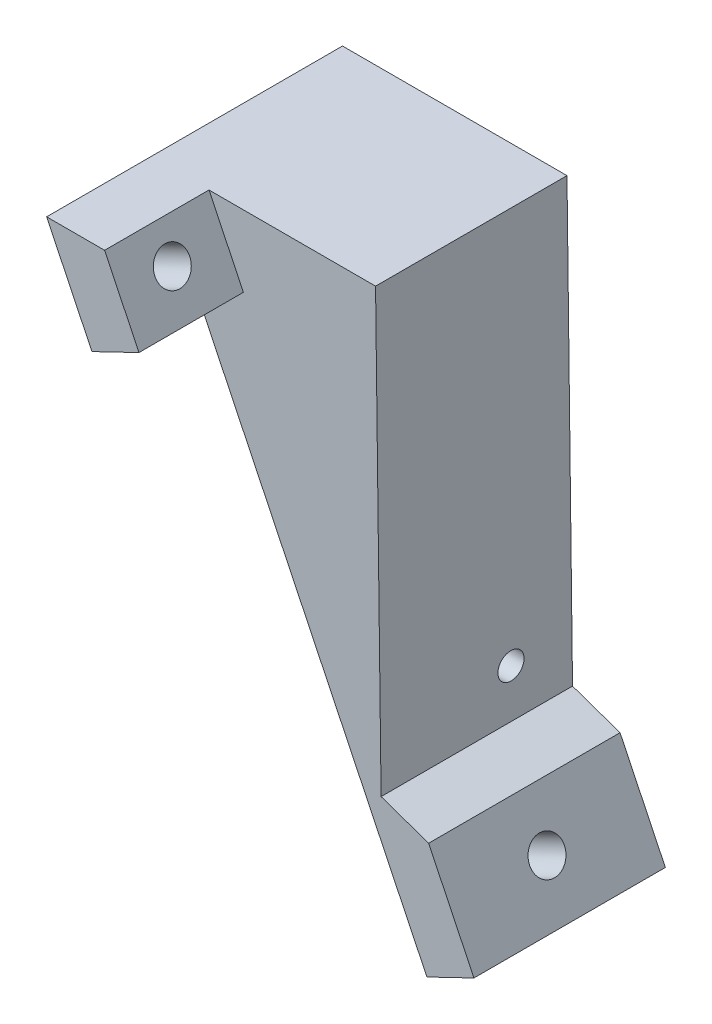
SolidWorks part; units mm, degrees
material "ABS"
ref_plane "Front Plane" through (0, 0, 0) normal (0, 0, 1) x (1, 0, 0)
ref_plane "Top Plane" through (0, 0, 0) normal (0, 1, 0) x (1, 0, 0)
ref_plane "Right Plane" through (0, 0, 0) normal (1, 0, 0) x (0, 0, -1)
sketch "Sketch1" plane through (0, 0, 0) normal (0, 0, 1) x (1, 0, 0)
  line L0 (-36.2386, 24.2413) -> (-9.7428, -30.7587)
  line L1 (-9.7428, -30.7587) -> (-10.436, 24.2413)
  line L2 (-10.436, 24.2413) -> (-36.2386, 24.2413)
  dimension "D1" = 55
  dimension "D2" = 55
  dimension "D3" = 25
extrude "Boss-Extrude1" add sketch "Sketch1" along normal blind 22
sketch "Sketch6" plane through (-19.9343, -9.6032, 0) normal (-0.9009, -0.434, 0) x (0, 0, 1)
  line L0 (22, 37.5671) -> (22, -23.4823) construction
  line L1 (34, 37.5671) -> (22, 37.5671)
  line L2 (34, 37.5671) -> (34, 25.5671)
  line L3 (34, 25.5671) -> (22, 25.5671)
  line L4 (22, 37.5671) -> (22, 25.5671)
  line L5 (0, -23.4823) -> (22, -23.4823)
  line L6 (0, -23.4823) -> (0, -35.4823)
  line L7 (0, -35.4823) -> (22, -35.4823)
  line L8 (22, -23.4823) -> (22, -35.4823)
  line L9 (22, 37.5671) -> (0, 37.5671) construction
  dimension "D1" = 12
  dimension "D2" = 12
  dimension "D3" = 0
  dimension "D4" = 12
  dimension "D5" = 0
  dimension "D6" = 0
extrude "Boss-Extrude4" add sketch "Sketch6" against normal blind 6
sketch "Sketch8" plane through (0, 0, 0) normal (0, 0, -1) x (-1, 0, 0)
  line L0 (9.7428, -30.7587) -> (4.3373, -28.1546)
  line L1 (4.3373, -28.1546) -> (9.7996, -26.2474)
  line L2 (9.7428, -30.7587) -> (10.436, 24.2413) construction
  line L3 (9.7996, -26.2474) -> (9.7428, -30.7587)
extrude "Boss-Extrude5" add sketch "Sketch8" against normal up to vertex (22 mm away) up to point (-10.436, 24.2413, 22)
sketch "Sketch9" plane through (-14.5288, -6.9992, 0) normal (0.9009, 0.434, 0) x (0, 0, -1)
  line L2 (-22, 25.5671) -> (-34, 25.5671) construction
  line L3 (0, -35.4823) -> (-22, -35.4823) construction
  line L4 (-22, -35.4823) -> (-22, -23.4823) construction
  circle A0 centre (-28, 30.5671) radius 2
  circle A1 centre (-11, -29.4823) radius 2
  point P9 (-28, 25.5671)
  point P12 (-11, -35.4823)
  point P15 (-22, -29.4823)
  dimension "D1" = 4
  dimension "D2" = 4
  dimension "D3" = 5
  dimension "D4" = 0
  dimension "D5" = 0
  dimension "D6" = 0
extrude "Cut-Extrude9" cut sketch "Sketch9" against normal blind 6
sketch "Sketch10" plane through (-10.1288, -0.1277, 0) normal (0.9999, 0.0126, 0) x (0, 0, -1)
  line L0 (-22, 24.3709) -> (0, 24.3709) construction
  line L1 (0, -26.1218) -> (0, 24.3709) construction
  circle A0 centre (-7, -20.6291) radius 1.5
  dimension "D1" = 3
  dimension "D3" = 7
  dimension "D2" = 45
extrude "Cut-Extrude10" cut sketch "Sketch10" against normal blind 36
sketch "Sketch12" plane through (0, 0, 22) normal (0, 0, -1) x (-1, 0, 0)
  line L0 (30.8332, 26.8454) -> (29.5787, 24.2413)
  line L1 (29.5787, 24.2413) -> (36.2386, 24.2413)
  line L2 (36.2386, 24.2413) -> (30.8332, 26.8454)
extrude "Cut-Extrude11" cut sketch "Sketch12" against normal blind 20
